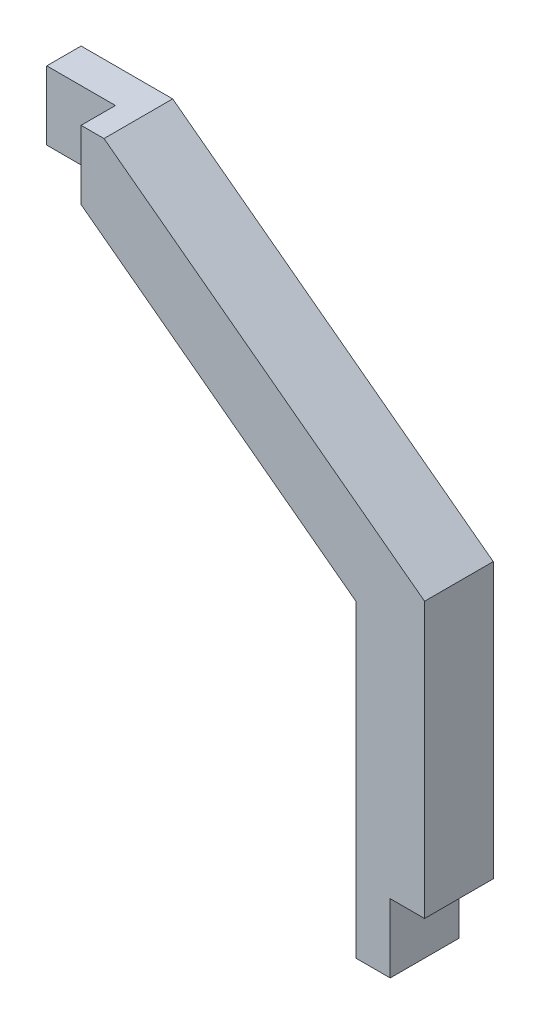
SolidWorks part; units mm, degrees
ref_plane "Alzado" through (0, 0, 0) normal (0, 0, 1) x (1, 0, 0)
ref_plane "Planta" through (0, 0, 0) normal (0, 1, 0) x (1, 0, 0)
ref_plane "Vista lateral" through (0, 0, 0) normal (1, 0, 0) x (0, 0, -1)
sketch "Croquis1" plane through (0, 0, 0) normal (0, 0, 1) x (1, 0, 0)
  line L0 (-60, 0) -> (60, 0) construction
  line L1 (-60, 0) -> (-33.3333, 0)
  line L2 (-33.3333, 0) -> (60, -70)
  line L3 (60, -70) -> (60, -170)
  line L4 (60, -170) -> (40, -170)
  line L5 (40, -170) -> (40, -80)
  line L6 (40, -80) -> (-40, -20)
  line L7 (-40, -20) -> (-60, -20)
  line L8 (-60, -20) -> (-60, 0)
  line L9 (60, -170) -> (60, -160) construction
  point P0 (-60, -10)
  point P3 (0, 0)
  point P4 (0, 0)
  point P15 (0, 0)
  dimension "D1" = 150
  dimension "D2" = 120
  dimension "D3" = 20
  dimension "D4" = 20
  dimension "D5" = 20
  dimension "D6" = 90
  dimension "D7" = 20
  dimension "D8" = 10
extrude "Saliente-Extruir1" add sketch "Croquis1" along normal blind 20 contours L1 L2 L3 L4 L5 L6 L7 L8
sketch "Croquis2" plane through (0, 0, 20) normal (0, 0, 1) x (1, 0, 0)
  line L0 (-60, -20) -> (-40, -20)
  line L1 (-40, -20) -> (-40, 0)
  line L2 (-60, 0) -> (-33.3333, 0) construction
  line L3 (-40, 0) -> (-60, 0)
  line L4 (-60, 0) -> (-60, -20)
extrude "Cortar-Extruir1" cut sketch "Croquis2" against normal blind 10
sketch "Croquis3" plane through (60, 0, 0) normal (1, 0, 0) x (0, 0, -1)
  line L0 (-20, -170) -> (0, -170)
  line L1 (0, -170) -> (0, -150)
  line L2 (0, -70) -> (0, -170) construction
  line L3 (0, -150) -> (-20, -150)
  line L4 (-20, -70) -> (-20, -170) construction
  line L5 (-20, -150) -> (-20, -170)
  dimension "D1" = 20
extrude "Cortar-Extruir2" cut sketch "Croquis3" against normal blind 10
